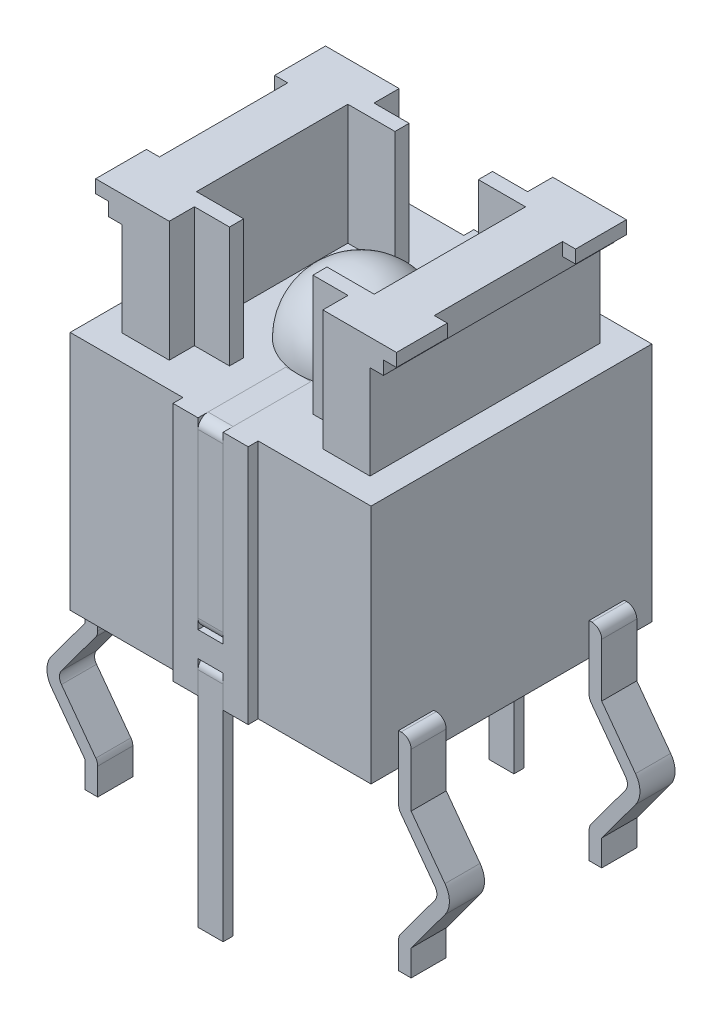
SolidWorks part; units mm, degrees
other "Camera1"
ref_plane "Front Plane" through (0, 0, 0) normal (0, 0, 1) x (1, 0, 0)
ref_plane "Top Plane" through (0, 0, 0) normal (0, 1, 0) x (1, 0, 0)
ref_plane "Right Plane" through (0, 0, 0) normal (1, 0, 0) x (0, 0, -1)
sketch "Sketch1" plane through (0, 0, 0) normal (0, 1, 0) x (1, 0, 0)
  line L1 (-3, 3) -> (3, 3)
  line L2 (-3, 3) -> (-3, -3)
  line L3 (-3, -3) -> (3, -3)
  line L4 (3, 3) -> (3, -3)
  line L5 (-3, 3) -> (3, -3) construction
  line L6 (-3, -3) -> (3, 3) construction
  point P0 (0, 0)
  dimension "D1" = 6
extrude "Boss-Extrude1" add sketch "Sketch1" along normal blind 4.8
sketch "Sketch3" plane through (0, 4.8, 0) normal (0, 1, 0) x (1, 0, 0)
  line L0 (-3.0107, 2.539) -> (2.9893, 2.539) construction
  dimension "D1" = 6
sketch "Sketch4" plane through (0, 0, 0) normal (0, 1, 0) x (1, 0, 0)
  line L0 (0, 0) -> (0, -3) construction
  line L1 (-3, -3) -> (3, -3) construction
  line L2 (3, 0) -> (-0.0876, 0) construction
  line L3 (3, -3) -> (3, 3) construction
  line L4 (1.7715, 1.5089) -> (1.7715, -1.5089)
  line L5 (1.7715, -1.5089) -> (0.8315, -1.5089)
  line L6 (1.7715, 1.5089) -> (0.8315, 1.5089)
  line L7 (0.8315, -1.5089) -> (0.8315, -1.7909)
  line L8 (0.8315, 1.5089) -> (0.8315, 1.7909)
  line L9 (0.8315, -1.7909) -> (1.5313, -1.7909)
  line L10 (0.8315, 1.7909) -> (1.5313, 1.7909)
  line L11 (1.5313, -1.7909) -> (1.5313, -2.2923)
  line L12 (1.5313, 1.7909) -> (1.5313, 2.2923)
  line L13 (1.5313, -2.2923) -> (3, -2.2923)
  line L14 (1.5313, 2.2923) -> (3, 2.2923)
  line L15 (3, -2.2923) -> (3, -1.2791)
  line L16 (3, 2.2923) -> (3, 1.2791)
  line L17 (3, -1.2791) -> (2.4713, -1.2791)
  line L18 (3, 1.2791) -> (2.4713, 1.2791)
  line L19 (2.4713, -1.2791) -> (2.4713, 1.2791)
  line L20 (-2.4713, -1.2791) -> (-2.4713, 1.2791)
  line L21 (-3, 1.2791) -> (-2.4713, 1.2791)
  line L22 (-3, -1.2791) -> (-2.4713, -1.2791)
  line L23 (-3, 2.2923) -> (-3, 1.2791)
  line L24 (-3, -2.2923) -> (-3, -1.2791)
  line L25 (-1.5313, 2.2923) -> (-3, 2.2923)
  line L26 (-1.5313, -2.2923) -> (-3, -2.2923)
  line L27 (-1.5313, 1.7909) -> (-1.5313, 2.2923)
  line L28 (-1.5313, -1.7909) -> (-1.5313, -2.2923)
  line L29 (-0.8315, 1.7909) -> (-1.5313, 1.7909)
  line L30 (-0.8315, -1.7909) -> (-1.5313, -1.7909)
  line L31 (-0.8315, 1.5089) -> (-0.8315, 1.7909)
  line L32 (-0.8315, -1.5089) -> (-0.8315, -1.7909)
  line L33 (-1.7715, 1.5089) -> (-0.8315, 1.5089)
  line L34 (-1.7715, -1.5089) -> (-0.8315, -1.5089)
  line L35 (-1.7715, 1.5089) -> (-1.7715, -1.5089)
  point P12 (1.7715, 0)
  point P26 (2.4713, 0)
  point P27 (-2.4713, 0)
  point P28 (-1.7715, 0)
extrude "Boss-Extrude2" add sketch "Sketch4" along normal blind 7.2
sketch "Sketch5" plane through (0, 0, 2.2923) normal (0, 0, 1) x (1, 0, 0)
  line L0 (-3, 7.2) -> (-3, 6.94)
  line L1 (-3, 7.2) -> (-3, 4.8) construction
  line L2 (-3, 6.94) -> (-2.74, 6.94)
  line L3 (-2.74, 6.94) -> (-2.74, 6.6725)
  line L4 (-2.74, 6.6725) -> (-2.4713, 6.6725)
  line L5 (-2.4713, 6.6725) -> (-2.4713, 4.8)
  line L6 (-3, 4.8) -> (3, 4.8) construction
  line L7 (-2.4713, 4.8) -> (-3, 4.8)
  line L8 (-3, 4.8) -> (-3, 6.94)
  line L9 (0, 4.8) -> (0, 6.4922) construction
  line L10 (-2.4713, 7.2) -> (-2.4713, 4.8) construction
  line L11 (-3, 7.2) -> (-1.5313, 7.2) construction
  line L12 (3, 4.8) -> (3, 6.94)
  line L13 (2.4713, 4.8) -> (3, 4.8)
  line L14 (2.4713, 6.6725) -> (2.4713, 4.8)
  line L15 (2.74, 6.6725) -> (2.4713, 6.6725)
  line L16 (2.74, 6.94) -> (2.74, 6.6725)
  line L17 (3, 6.94) -> (2.74, 6.94)
  line L18 (3, 7.2) -> (3, 6.94)
  line M11 (-3, 7.2) -> (-3, 4.8)
  dimension "D1" = 0.26
  dimension "D2" = 0.26
  dimension "D3" = 0.2675
extrude "Cut-Extrude1" cut sketch "Sketch5" against normal through all contours L7 L5 L4 L3 L2 M11 | L12 L17 L16 L15 L14 L13 region at (-2.7445, 5.8065, 2.2923) region at (2.7445, 5.8065, 2.2923)
sketch "Sketch6" plane through (0, 0, 3) normal (0, 0, 1) x (1, 0, 0)
  line L0 (-3, 0.649) -> (-3, -0.6342)
  line L1 (-3, 4.8) -> (-3, 0) construction
  line L2 (-3.0391, -0.7529) -> (-3.724, -1.6813)
  line L3 (-3.724, -1.9187) -> (-3.0391, -2.8471)
  line L4 (-3, -2.9658) -> (-3, -3.5)
  line L6 (-3, 0) -> (3, 0) construction
  arc A0 (-3.0391, -2.8471) -> (-3, -2.9658) centre (-3.2, -2.9658) cw
  arc A1 (-3.724, -1.6813) -> (-3.724, -1.9187) centre (-3.563, -1.8) ccw
  arc A2 (-3, -0.6342) -> (-3.0391, -0.7529) centre (-3.2, -0.6342) cw
  point P12 (-3, -2.9)
  point P16 (-3.8116, -1.8)
  point P20 (-3, -0.7)
  dimension "D4" = 0.2
  dimension "D1" = 0.6
  dimension "D2" = 0.7
  dimension "D3" = 1.8
extrude "Extrude-Thin2" add sketch "Sketch6" against normal blind 0.7 from offset 0.75 separate body thin offset against normal yes thin type one direction wall 0.25
fillet "Fillet1" radius 0.2 1 edges at (-3.25, 0.649, 1.9)
mirror "Mirror3" about plane through (0, 0, 0) normal (0, 0, 1) of bodies 107
mirror "Mirror4" about plane through (0, 0, 0) normal (1, 0, 0) of bodies 107 108
sketch "Sketch7" plane through (0, 0, 0) normal (1, 0, 0) x (0, 0, -1)
  line L0 (-3, 0.649) -> (-3, -4)
  line L1 (-3, 4.8) -> (-3, 0) construction
  line L2 (-3, 0) -> (3, 0) construction
  dimension "D1" = 4
sketch "Sketch8" plane through (0, 4.8, 0) normal (0, 1, 0) x (1, 0, 0)
  line L0 (-3, -3) -> (3, -3) construction
  line L1 (0.75, -3) -> (3, -3)
  line L2 (0.75, -3) -> (0.75, -2.8)
  line L3 (0.75, -2.8) -> (3, -2.8)
  line L4 (3, -3) -> (3, -2.8)
  line L5 (3, -3) -> (3, 3) construction
  line L6 (-3, 3) -> (-3, -3) construction
  line L7 (-0.75, -3) -> (-3, -3)
  line L8 (-0.75, -3) -> (-0.75, -2.8)
  line L9 (-0.75, -2.8) -> (-3, -2.8)
  line L10 (-3, -3) -> (-3, -2.8)
  line L11 (3, 3) -> (-3, 3) construction
  line L12 (-0.75, 3) -> (-3, 3)
  line L13 (-0.75, 3) -> (-0.75, 2.8)
  line L14 (-0.75, 2.8) -> (-3, 2.8)
  line L15 (-3, 3) -> (-3, 2.8)
  line L16 (-0.25, -3.15) -> (-0.25, -3) construction
  line L17 (0.75, 3) -> (3, 3)
  line L18 (0.75, 3) -> (0.75, 2.8)
  line L19 (0.75, 2.8) -> (3, 2.8)
  line L20 (3, 3) -> (3, 2.8)
  line L21 (0.25, -3.15) -> (0.25, -3) construction
  dimension "D1" = 0.5
  dimension "D2" = 0.5
  dimension "D3" = 0.2
  dimension "D4" = 0.2
extrude "Cut-Extrude2" cut sketch "Sketch8" against normal through all
sketch "Sketch9" plane through (0, 0, 3) normal (0, 0, 1) x (1, 0, 0)
  line L0 (-0.75, 0) -> (0.75, 0) construction
  line L1 (-0.25, 4.8) -> (0.25, 4.8)
  line L2 (-0.25, 4.8) -> (-0.25, 0)
  line L3 (-0.25, 0) -> (0.25, 0)
  line L4 (0.25, 4.8) -> (0.25, 0)
  line L5 (-0.25, 4.8) -> (0.25, 0) construction
  line L6 (-0.25, 0) -> (0.25, 4.8) construction
  point P0 (0, 2.4)
  dimension "D1" = 0.5
extrude "Cut-Extrude3" cut sketch "Sketch9" against normal blind 0.2
mirror "Mirror5" about plane through (0, 0, 0) normal (0, 0, 1) of "Cut-Extrude3"
extrude "Extrude-Thin4" add sketch "Sketch7" along normal mid plane 0.5 separate body thin thin type one direction reverse wall 0.2
fillet "Fillet2" radius 0.2 1 edges at (0, 0.649, 3)
mirror "Mirror6" about plane through (0, 0, 0) normal (0, 0, 1) of bodies 115
sketch "Sketch10" plane through (0, 4.8, 0) normal (0, 1, 0) x (1, 0, 0)
  line L0 (0, 1.25) -> (0, -1.25) construction
  line L1 (0, 1.25) -> (0, -1.25)
  arc A0 (0, 1.25) -> (0, -1.25) centre (0, 0) ccw
  dimension "D1" = 2.5
revolve "Revolve1" add sketch "Sketch10" angle 180 about L0 reverse direction yes
sketch "Sketch11" plane through (0, 0, 2.8) normal (0, 0, 1) x (1, 0, 0)
  line L0 (-0.25, 4.8) -> (-0.25, 0) construction
  line L1 (-0.25, 0.6411) -> (0.25, 0.6411)
  line L2 (-0.25, 0.6411) -> (-0.25, 1.1411)
  line L3 (-0.25, 1.1411) -> (0.25, 1.1411)
  line L4 (0.25, 0.6411) -> (0.25, 1.1411)
  line L5 (0.25, 0) -> (0.25, 4.8) construction
  dimension "D1" = 0.5
extrude "Boss-Extrude3" add sketch "Sketch11" along normal up to surface (0.2 mm away) separate body up to face at (-0.5, 2.4, 3)
mirror "Mirror7" about plane through (0, 0, 0) normal (0, 0, 1) of bodies 118
combine bodies "Combine1" operation type add bodies to combine 117 118 119
sketch "Sketch12" plane through (0, 0, 2.8) normal (0, 0, 1) x (1, 0, 0)
  line L0 (-0.25, 4.8) -> (-0.25, 1.1411) construction
  line L1 (-0.25, 4.4893) -> (0.25, 4.4893)
  line L2 (-0.25, 4.4893) -> (-0.25, 1.1411)
  line L3 (-0.25, 1.1411) -> (0.25, 1.1411)
  line L4 (0.25, 4.4893) -> (0.25, 1.1411)
sketch "Sketch13" plane through (2.4713, 0, 0) normal (1, 0, 0) x (0, 0, -1)
  line L1 (-1.2791, 7.2) -> (1.2791, 7.2)
  line L2 (-1.2791, 7.2) -> (-1.2791, 6.6725)
  line L3 (-1.2791, 6.6725) -> (1.2791, 6.6725)
  line L4 (1.2791, 7.2) -> (1.2791, 6.6725)
extrude "Boss-Extrude5" add sketch "Sketch13" along normal up to surface (0.2687 mm away) separate body up to face at (2.74, 6.8062, -1.7857)
mirror "Mirror10" about plane through (0, 0, 0) normal (1, 0, 0) of bodies 123
combine bodies "Combine2" operation type add bodies to combine 125 120 123
sketch "Sketch14" plane through (0.25, 0, 0) normal (-1, 0, 0) x (0, 0, 1)
  line L0 (-3, 1.1411) -> (-3, 4.8)
  line L1 (-3, 4.8) -> (-1.25, 4.8)
  line L2 (-2.8, 4.8) -> (2.8, 4.8) construction
  arc A0 (1.25, 4.8) -> (-1.25, 4.8) centre (0, 4.8) ccw construction
extrude "Cut-Extrude-Thin1" cut sketch "Sketch14" along normal blind 0.5 thin thin type one direction wall 0.2
mirror "Mirror11" about plane through (0, 0, 0) normal (0, 0, 1) of "Cut-Extrude-Thin1"
extrude "Extrude-Thin5" add sketch "Sketch14<2>" along normal blind 0.5 separate body thin thin type one direction wall 0.2
sketch "Sketch14<2>" plane through (0.25, 0, 0) normal (-1, 0, 0) x (0, 0, 1) same geometry as "Sketch14"
fillet "Fillet3" radius 0.2 2 edges at (0, 4.8, -3) (0, 1.1411, -3)
mirror "Mirror15" about plane through (0, 0, 0) normal (0, 0, 1) of bodies 129
